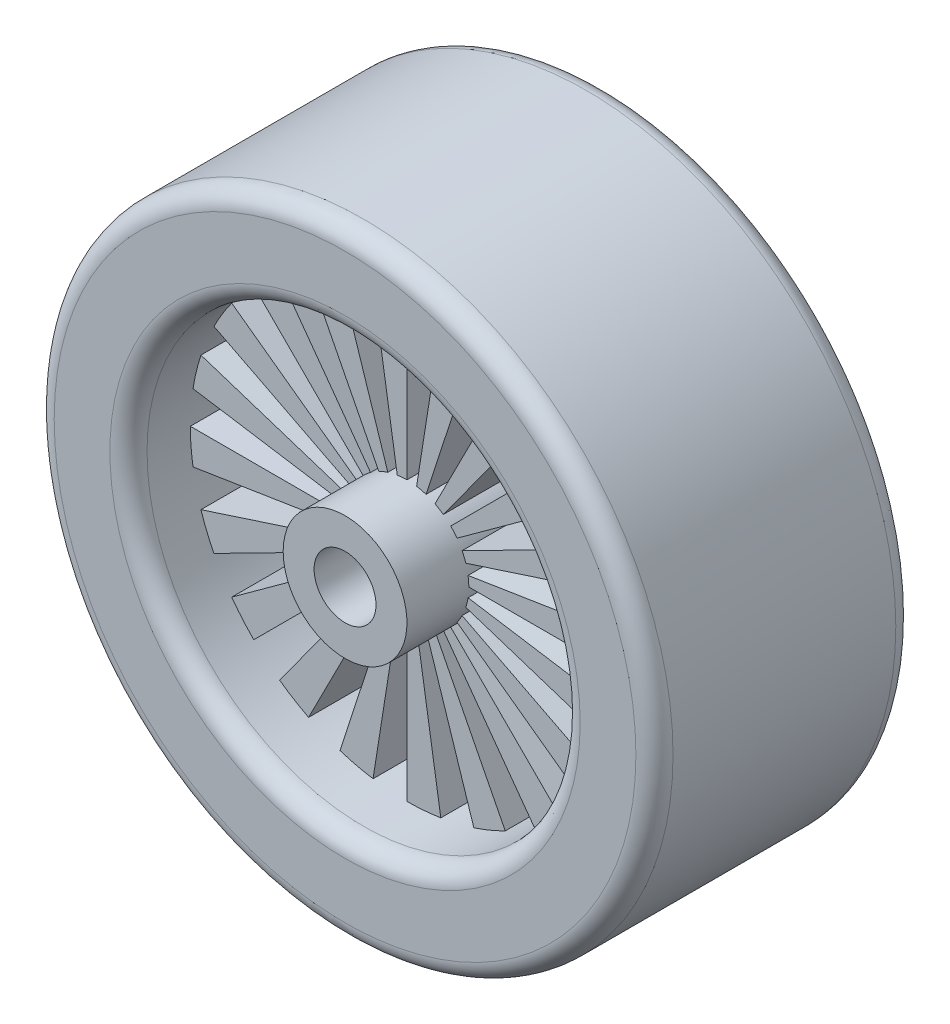
SolidWorks part; units mm, degrees
ref_plane "Front Plane" through (0, 0, 0) normal (0, 0, 1) x (1, 0, 0)
ref_plane "Top Plane" through (0, 0, 0) normal (0, 1, 0) x (1, 0, 0)
ref_plane "Right Plane" through (0, 0, 0) normal (1, 0, 0) x (0, 0, -1)
sketch "Sketch1" plane through (0, 0, 0) normal (0, 0, 1) x (1, 0, 0)
  circle A0 centre (0, 0) radius 500
extrude "Boss-Extrude1" add sketch "Sketch1" along normal blind 10 and the other way blind 10
sketch "Sketch2" plane through (0, 0, -10) normal (0, 0, -1) x (-1, 0, 0)
  circle A0 centre (0, 0) radius 500
  circle A1 centre (0, 0) radius 350
extrude "Boss-Extrude2" add sketch "Sketch2" along normal blind 200
sketch "Sketch3" plane through (0, 0, -10) normal (0, 0, -1) x (-1, 0, 0)
  circle A0 centre (0, 0) radius 100
extrude "Boss-Extrude3" add sketch "Sketch3" along normal blind 200
sketch "Sketch4" plane through (0, 0, -10) normal (0, 0, -1) x (-1, 0, 0)
  line L0 (-100, 0) -> (-350, 0)
  line L1 (-98.7688, 15.6434) -> (-345.6909, 54.7521)
  line L2 (-95.1057, 30.9017) -> (-332.8698, 108.1559)
  line L3 (-89.1007, 45.399) -> (-311.8523, 158.8967)
  line L4 (-80.9017, 58.7785) -> (-283.1559, 205.7248)
  line L5 (-70.7107, 70.7107) -> (-247.4874, 247.4874)
  line L6 (-58.7785, 80.9017) -> (-205.7248, 283.1559)
  line L7 (-45.399, 89.1007) -> (-158.8967, 311.8523)
  line L8 (-30.9017, 95.1057) -> (-108.1559, 332.8698)
  line L9 (-15.6434, 98.7688) -> (-54.7521, 345.6909)
  line L10 (0, 100) -> (0, 350)
  line L11 (15.6434, 98.7688) -> (54.7521, 345.6909)
  line L12 (30.9017, 95.1057) -> (108.1559, 332.8698)
  line L13 (45.399, 89.1007) -> (158.8967, 311.8523)
  line L14 (58.7785, 80.9017) -> (205.7248, 283.1559)
  line L15 (70.7107, 70.7107) -> (247.4874, 247.4874)
  line L16 (80.9017, 58.7785) -> (283.1559, 205.7248)
  line L17 (89.1007, 45.399) -> (311.8523, 158.8967)
  line L18 (95.1057, 30.9017) -> (332.8698, 108.1559)
  line L19 (98.7688, 15.6434) -> (345.6909, 54.7521)
  line L20 (100, 0) -> (350, 0)
  line L21 (98.7688, -15.6434) -> (345.6909, -54.7521)
  line L22 (95.1057, -30.9017) -> (332.8698, -108.1559)
  line L23 (89.1007, -45.399) -> (311.8523, -158.8967)
  line L24 (80.9017, -58.7785) -> (283.1559, -205.7248)
  line L25 (70.7107, -70.7107) -> (247.4874, -247.4874)
  line L26 (58.7785, -80.9017) -> (205.7248, -283.1559)
  line L27 (45.399, -89.1007) -> (158.8967, -311.8523)
  line L28 (30.9017, -95.1057) -> (108.1559, -332.8698)
  line L29 (15.6434, -98.7688) -> (54.7521, -345.6909)
  line L30 (0, -100) -> (0, -350)
  line L31 (-15.6434, -98.7688) -> (-54.7521, -345.6909)
  line L32 (-30.9017, -95.1057) -> (-108.1559, -332.8698)
  line L33 (-45.399, -89.1007) -> (-158.8967, -311.8523)
  line L34 (-58.7785, -80.9017) -> (-205.7248, -283.1559)
  line L35 (-70.7107, -70.7107) -> (-247.4874, -247.4874)
  line L36 (-80.9017, -58.7785) -> (-283.1559, -205.7248)
  line L37 (-89.1007, -45.399) -> (-311.8523, -158.8967)
  line L38 (-95.1057, -30.9017) -> (-332.8698, -108.1559)
  line L39 (-98.7688, -15.6434) -> (-345.6909, -54.7521)
  circle A0 centre (0, 0) radius 100 construction
  circle A1 centre (0, 0) radius 100 construction
  circle A2 centre (0, 0) radius 350 construction
  circle A3 centre (0, 0) radius 350
  circle A4 centre (0, 0) radius 100
  point P90 (0, 0)
  circle M42 centre (0, 0) radius 100
  circle M43 centre (0, 0) radius 350
  dimension "D1" = 40
extrude "Boss-Extrude4" add sketch "Sketch4" along normal blind 100 contours L1 L0 M42 M43 | L3 L2 M42 M43 | L5 L4 M42 M43 | L7 L6 M42 M43 | L9 L8 M42 M43 | L11 L10 M42 M43 | L13 L12 M42 M43 | L15 L14 M42 M43 | L17 L16 M42 M43 | L19 L18 M42 M43 | L21 L20 M42 M43 | L23 L22 M42 M43 | L25 L24 M42 M43 | L27 L26 M42 M43 | L29 L28 M42 M43 | L31 L30 M42 M43 | L33 L32 M42 M43 | L35 L34 M42 M43 | L37 L36 M42 M43 | L39 L38 M42 M43 region at (247.1289, 19.4495, -10) region at (241.0438, -57.8695, -10) region at (229.0234, 94.8646, -10) region at (211.3636, -129.5238, -10) region at (188.4994, 160.9937, -10) region at (160.9937, -188.4994, -10) region at (129.5238, 211.3636, -10) region at (94.8646, -229.0234, -10) region at (57.8695, 241.0438, -10) region at (19.4495, -247.1289, -10) region at (-19.4495, 247.1289, -10) region at (-57.8695, -241.0438, -10) region at (-94.8646, 229.0234, -10) region at (-129.5238, -211.3636, -10) region at (-160.9937, 188.4994, -10) region at (-188.4994, -160.9937, -10) region at (-211.3636, 129.5238, -10) region at (-229.0234, -94.8646, -10) region at (-241.0438, 57.8695, -10) region at (-247.1289, -19.4495, -10)
fillet "Fillet1" radius 30 2 edges at (-500, 0, -210) (-350, 0, -210)
mirror "Mirror1" about plane through (0, 0, 0) normal (0, 0, 1) of "Fillet1", "Boss-Extrude1", "Boss-Extrude3", "Boss-Extrude4", "Boss-Extrude2"
sketch "Sketch5" plane through (0, 0, 210) normal (0, 0, 1) x (1, 0, 0)
  circle A0 centre (0, 0) radius 50
extrude "Cut-Extrude1" cut sketch "Sketch5" against normal blind 200
